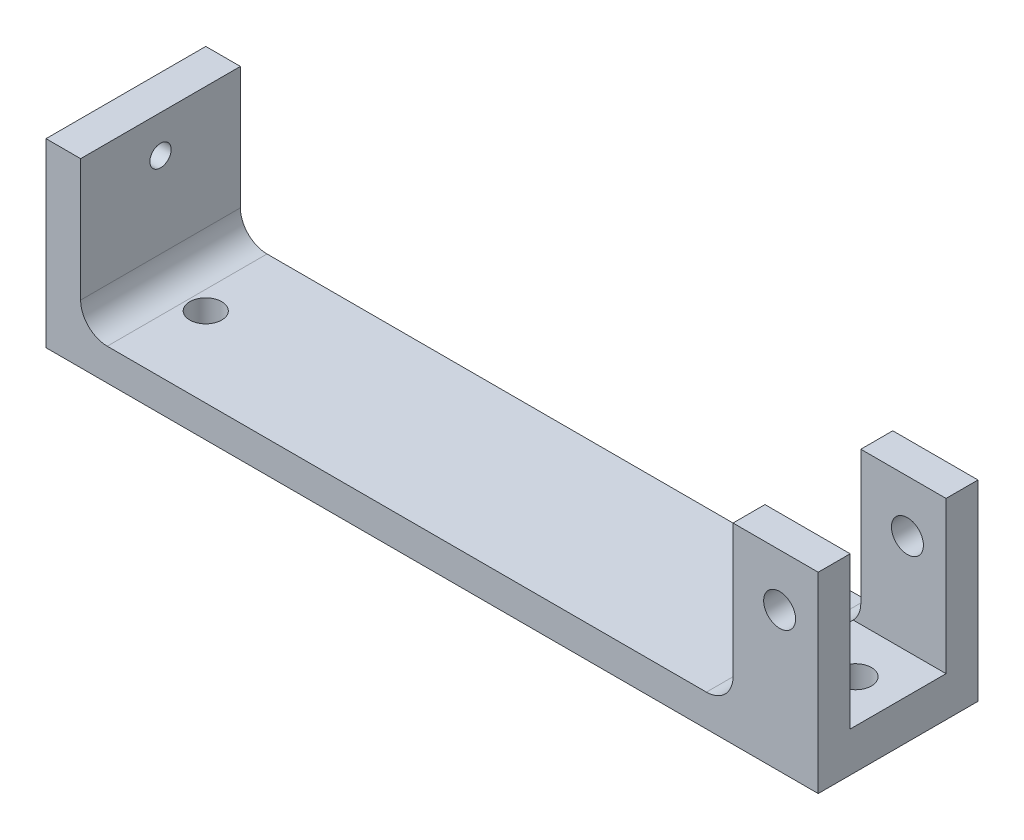
SolidWorks part; units mm, degrees
ref_plane "Front Plane" through (0, 0, 0) normal (0, 0, 1) x (1, 0, 0)
ref_plane "Top Plane" through (0, 0, 0) normal (0, 1, 0) x (1, 0, 0)
ref_plane "Right Plane" through (0, 0, 0) normal (1, 0, 0) x (0, 0, -1)
sketch "Sketch1" plane through (0, 0, 0) normal (0, 0, 1) x (1, 0, 0)
  line L0 (-72.5, 34) -> (-72.5, 0)
  line L1 (-72.5, 0) -> (72.5, 0)
  line L2 (72.5, 0) -> (72.5, 36)
  line L3 (72.5, 36) -> (56.5, 36)
  line L4 (56.5, 36) -> (56.5, 6)
  line L5 (56.5, 6) -> (-66, 6)
  line L6 (-66, 6) -> (-66, 34)
  line L7 (-66, 34) -> (-72.5, 34)
  dimension "D1" = 6.5
  dimension "D2" = 16
  dimension "D3" = 145
  dimension "D4" = 34
  dimension "D5" = 36
  dimension "D6" = 6
extrude "Boss-Extrude1" add sketch "Sketch1" along normal blind 15 and the other way blind 15
sketch "Sketch2" plane through (0, 0, 0) normal (0, 1, 0) x (1, 0, 0)
  line L0 (-57.5, 0) -> (64.5, 0) construction
  line L1 (-72.5, 15) -> (-72.5, -15) construction
  circle A0 centre (-57.5, 0) radius 3
  circle A1 centre (64.5, 0) radius 3
  dimension "D1" = 6
  dimension "D2" = 122
  dimension "D3" = 15
extrude "Cut-Extrude1" cut sketch "Sketch2" along normal through all
fillet "Fillet1" radius 5 2 edges at (56.5, 6, 0) (-66, 6, 0)
sketch "Sketch3" plane through (0, 36, 0) normal (0, 1, 0) x (1, 0, 0)
  line L0 (56.5, 15) -> (56.5, -15) construction
  line L1 (56.5, 9) -> (72.5, 9)
  line L2 (56.5, 9) -> (56.5, -9)
  line L3 (56.5, -9) -> (72.5, -9)
  line L4 (72.5, 9) -> (72.5, -9)
  line L5 (72.5, 15) -> (72.5, -15) construction
  line L6 (56.5, -9) -> (72.5, 9) construction
  line L7 (72.5, 15) -> (56.5, 15) construction
  line L8 (51.5, -15) -> (51.5, 15) construction
  line L9 (56.5, 9) -> (51.5, 9)
  line L10 (56.5, 9) -> (56.5, -9)
  line L11 (56.5, -9) -> (51.5, -9)
  line L12 (51.5, 9) -> (51.5, -9)
  circle A0 centre (64.5, 0) radius 3 construction
  point P10 (64.5, 0)
  circle M6 centre (64.5, 0) radius 3
  line M7 (56.5, 15) -> (56.5, -15)
  line M9 (72.5, -15) -> (72.5, 15)
  dimension "D1" = 6
extrude "Cut-Extrude2" cut sketch "Sketch3" against normal offset from surface (28.5 mm away) 7.5 contours L6 L1 M7 M6 | L9 L12 L11 M7 | L6 L3 M9 M6 region at (61.6466, 36, -3.2345) region at (54, 36, 0) region at (67.3534, 36, 3.2345) up to face at (-57.5, 0, 3)
sketch "Sketch4" plane through (0, 0, 0) normal (0, 0, 1) x (1, 0, 0)
  line L0 (72.5, 36) -> (56.5, 36) construction
  line L4 (72.5, 0) -> (72.5, 36) construction
  circle A0 centre (65.25, 26.25) radius 3
  circle A1 centre (65.25, 26.25) radius 4.25 construction
  point P7 (0, 0)
  dimension "D1" = 6
  dimension "D2" = 8.5
  dimension "D3" = 9.75
  dimension "D4" = 7.25
extrude "Cut-Extrude3" cut sketch "Sketch4" against normal through all both and the other way through all
sketch "Sketch5" plane through (0, 0, 0) normal (1, 0, 0) x (0, 0, -1)
  line L0 (0, 0) -> (0, 27) construction
  circle A0 centre (0, 27) radius 2
  dimension "D1" = 4
  dimension "D2" = 27
extrude "Cut-Extrude4" cut sketch "Sketch5" against normal through all
